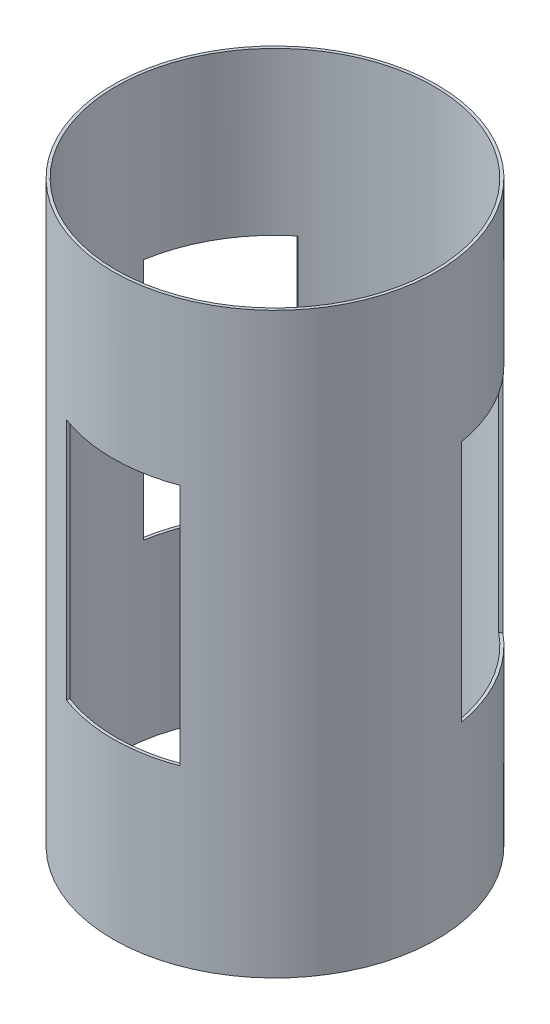
SolidWorks part; units mm, degrees
material "Carbon Fiber"
ref_plane "Front Plane" through (0, 0, 0) normal (0, 0, 1) x (1, 0, 0)
ref_plane "Top Plane" through (0, 0, 0) normal (0, 1, 0) x (1, 0, 0)
ref_plane "Right Plane" through (0, 0, 0) normal (1, 0, 0) x (0, 0, -1)
sketch "Sketch1" plane through (0, 0, 0) normal (0, 1, 0) x (1, 0, 0)
  line L0 (0, 0) -> (0, -68.75) construction
  line L1 (68.75, 0) -> (-68.75, 0) construction
  line L2 (-56.7965, 32.7915) -> (-44.5606, 53.9848)
  line L3 (0, 0) -> (59.5392, 34.375) construction
  line L4 (0, 0) -> (-59.5392, 34.375) construction
  line L5 (-44.5606, 53.9848) -> (-69.0325, 11.5982)
  line L6 (-54.2965, 37.1216) -> (-59.2965, 28.4614)
  line L7 (-59.2965, 28.4614) -> (-42.7188, 18.8902)
  line L8 (0, -65.583) -> (-24.4719, -65.583)
  line L9 (-24.4719, -65.583) -> (24.4719, -65.583)
  line L10 (-42.7188, 18.8902) -> (-37.7188, 27.5505)
  line L11 (-59.2965, 28.4614) -> (-61.8816, 29.9538)
  line L12 (-54.2965, 37.1216) -> (-37.7188, 27.5505)
  line L13 (-51.7965, 41.4517) -> (-55, 43.3013)
  line L14 (-61.7965, 24.1312) -> (-65, 25.9808)
  line L15 (-51.7965, 41.4517) -> (-30.8887, 29.3806) construction
  line L16 (-40.8887, 12.0601) -> (-30.8887, 29.3806) construction
  line L17 (-61.7965, 24.1312) -> (-40.8887, 12.0601) construction
  line L18 (56.7965, 32.7915) -> (69.0325, 11.5982)
  line L19 (69.0325, 11.5982) -> (44.5606, 53.9848)
  line L20 (59.2965, 28.4614) -> (54.2965, 37.1216)
  line L21 (54.2965, 37.1216) -> (37.7188, 27.5505)
  line L22 (37.7188, 27.5505) -> (42.7188, 18.8902)
  line L23 (54.2965, 37.1216) -> (56.8816, 38.6141)
  line L24 (59.2965, 28.4614) -> (42.7188, 18.8902)
  line L25 (61.7965, 24.1312) -> (65, 25.9808)
  line L26 (-5, -65.583) -> (5, -65.583)
  line L27 (5, -65.583) -> (5, -46.4407)
  line L28 (5, -46.4407) -> (-5, -46.4407)
  line L29 (5, -65.583) -> (5, -68.5679)
  line L30 (-5, -65.583) -> (-5, -46.4407)
  line L32 (51.7965, 41.4517) -> (55, 43.3013)
  line L33 (61.7965, 24.1312) -> (40.8887, 12.0601) construction
  line L34 (30.8887, 29.3806) -> (40.8887, 12.0601) construction
  line L35 (51.7965, 41.4517) -> (30.8887, 29.3806) construction
  line L36 (-24.4719, -65.583) -> (-24.4719, -64.2471)
  line L37 (24.4719, -65.583) -> (24.4719, -64.2471)
  line L38 (-69.0325, 11.5982) -> (-67.8756, 10.9302)
  line L39 (-10, -10) -> (10, -10)
  line L40 (-10, -10) -> (-10, 10)
  line L41 (-10, 10) -> (10, 10)
  line L42 (10, -10) -> (10, 10)
  line L43 (-10, -10) -> (10, 10) construction
  line L44 (-10, 10) -> (10, -10) construction
  line L45 (-44.5606, 53.9848) -> (-43.4036, 53.3168)
  line L46 (44.5606, 53.9848) -> (-67.8756, -10.9302)
  line L47 (69.0325, 11.5982) -> (67.8756, 10.9302)
  line L58 (-10, -65.583) -> (-10, -41.4407) construction
  line L59 (10, -41.4407) -> (-10, -41.4407) construction
  line L60 (10, -65.583) -> (10, -41.4407) construction
  line L61 (-10, -65.583) -> (-10, -69.282)
  line L62 (10, -65.583) -> (10, -69.282)
  line L63 (10, -65.583) -> (10, -68.5679) construction
  circle A0 centre (0, 0) radius 68.75
  circle A1 centre (0, 0) radius 70
  circle A2 centre (0, 0) radius 66.5
  point P14 (0, 0)
  point P26 (-40.2188, 23.2204)
  point P39 (0, -46.4407)
  point P51 (40.2188, 23.2204)
  point P58 (0, 0)
  point P67 (0, 0)
  point P68 (0, 0)
  point P71 (0, 0)
  point P81 (0, 0)
  dimension "D1" = 137.5
  dimension "D2" = 140
  dimension "D3" = 50
  dimension "D5" = 30
  dimension "D9" = 133
  dimension "D8" = 3
  dimension "D10" = 22.3093
  dimension "D4" = 30
  dimension "D7" = 5
  dimension "D6" = 5
extrude "Boss-Extrude7" add sketch "Sketch1" along normal blind 105 separate body contours L46 A1 L45 A0 | L37 A1 L47 A0 | L38 A1 L36 A0 region at (0, 0, -69.0933) region at (-68.9021, 0, -10.4882) region at (68.8647, 0, -5.7447)
sketch "Sketch16" plane through (0, 105, 0) normal (0, 1, 0) x (-1, 0, 0)
  line L0 (24.4719, 65.583) -> (-24.4719, 65.583)
  line L1 (5, 65.583) -> (5, 46.4407)
  line L2 (5, 46.4407) -> (-5, 46.4407)
  line L3 (-5, 46.4407) -> (-5, 68.5679)
  line L4 (0, 68.75) -> (0, 0) construction
  line L5 (68.75, 0) -> (-68.75, 0) construction
  line L7 (10, -10) -> (-10, -10)
  line L8 (10, -10) -> (10, 10)
  line L9 (10, 10) -> (-10, 10)
  line L10 (-10, -10) -> (-10, 10)
  line L11 (10, -10) -> (-10, 10) construction
  line L13 (10, 10) -> (-10, -10) construction
  line L14 (0, 0) -> (-59.5392, -34.375) construction
  line L15 (0, 0) -> (59.5392, -34.375) construction
  line L16 (0, 65.583) -> (0, 51.4407) construction
  line L17 (0, 51.4407) -> (-1.7959, 51.4407) construction
  line L18 (-1.7959, 51.4407) -> (-10, 69.282) construction
  line L19 (69.0325, -11.5982) -> (44.5606, -53.9848)
  line L20 (44.5606, -53.9848) -> (54.2965, -37.1216)
  line L21 (54.2965, -37.1216) -> (37.7188, -27.5505)
  line L22 (37.7188, -27.5505) -> (42.7188, -18.8902)
  line L23 (42.7188, -18.8902) -> (61.8816, -29.9538)
  line L25 (-5, 46.4407) -> (-13.4627, 64.8443) construction
  line L27 (-1.7959, 51.4407) -> (-8.9199, 66.9332) construction
  line L28 (65, -25.9808) -> (40.8887, -12.0601) construction
  line L29 (40.8887, -12.0601) -> (30.8887, -29.3806) construction
  line L30 (30.8887, -29.3806) -> (55, -43.3013) construction
  line L31 (-44.5606, -53.9848) -> (-69.0325, -11.5982)
  line L32 (-56.8816, -38.6141) -> (-37.7188, -27.5505)
  line L33 (-37.7188, -27.5505) -> (-42.7188, -18.8902)
  line L34 (-42.7188, -18.8902) -> (-59.2965, -28.4614)
  line L38 (-55, -43.3013) -> (-30.8887, -29.3806) construction
  line L39 (-30.8887, -29.3806) -> (-40.8887, -12.0601) construction
  line L40 (-40.8887, -12.0601) -> (-65, -25.9808) construction
  circle A2 centre (0, 0) radius 68.75
  circle A3 centre (0, 0) radius 67.5
  dimension "D1" = 137.5
  dimension "D2" = 135
  dimension "D3" = 5
ref_axis "Axis1" through (59.5392, 105, -34.375) along (-0.0261, -0.9995, 0.0151)
extrude "Boss-Extrude8" add sketch "Sketch1<22>" along normal blind 70 from surface contours A0 L45 L5 | L5 A1 L13 A0 | L13 A1 L14 A0 | L14 A1 L5 A0 | A0 L5 L38 | L38 A1 L36 A0 | A0 L36 L9 | L9 A1 L61 A0 | L61 A1 L62 A0 | A0 L9 L37 | L62 A1 L9 A0 | L37 A1 L47 A0 | A0 L47 L19 | L19 A1 L25 A0 | L25 A1 L32 A0 | L32 A1 L19 A0 | A0 L19 L46 | L46 A1 L45 A0 region at (-59.8712, 0, -34.5667) region at (-50.1141, 0, -47.8682) region at (-44.8114, 0, -52.6736) region at (-68.0224, 0, -12.471) region at (-66.5122, 0, -19.4659) region at (0, 0, -69.0933) region at (44.8114, 0, -52.6736) region at (-68.9021, 0, -10.4882) region at (50.1141, 0, -47.8682) region at (-23.2109, 0, 65.1446) region at (-16.3981, 0, 67.3342) region at (59.8712, 0, -34.5667) region at (0, 0, 69.1333) region at (66.5122, 0, -19.4659) region at (16.3981, 0, 67.3342) region at (68.0224, 0, -12.471) region at (68.8647, 0, -5.7447) region at (23.2109, 0, 65.1446) starting at face at (53.2717, 105, 30.7565)
sketch "Sketch1<22>" plane through (0, 0, 0) normal (0, 1, 0) x (1, 0, 0) same geometry as "Sketch1"
extrude "Boss-Extrude9" add sketch "Sketch1<23>" against normal blind 75 contours L5 A1 L13 A0 | L13 A1 L14 A0 | L14 A1 L5 A0 | A0 L5 L38 | L38 A1 L36 A0 | A0 L45 L5 | L46 A1 L45 A0 | A0 L19 L46 | L32 A1 L19 A0 | L25 A1 L32 A0 | L19 A1 L25 A0 | A0 L47 L19 | L37 A1 L47 A0 | A0 L36 L9 | L9 A1 L61 A0 | L61 A1 L62 A0 | A0 L9 L37 | L62 A1 L9 A0 region at (-59.8712, 0, -34.5667) region at (-50.1141, 0, -47.8682) region at (-44.8114, 0, -52.6736) region at (-68.0224, 0, -12.471) region at (-66.5122, 0, -19.4659) region at (0, 0, -69.0933) region at (44.8114, 0, -52.6736) region at (-68.9021, 0, -10.4882) region at (50.1141, 0, -47.8682) region at (-23.2109, 0, 65.1446) region at (-16.3981, 0, 67.3342) region at (59.8712, 0, -34.5667) region at (0, 0, 69.1333) region at (66.5122, 0, -19.4659) region at (16.3981, 0, 67.3342) region at (68.0224, 0, -12.471) region at (68.8647, 0, -5.7447) region at (23.2109, 0, 65.1446)
sketch "Sketch1<23>" plane through (0, 0, 0) normal (0, 1, 0) x (1, 0, 0) same geometry as "Sketch1"
